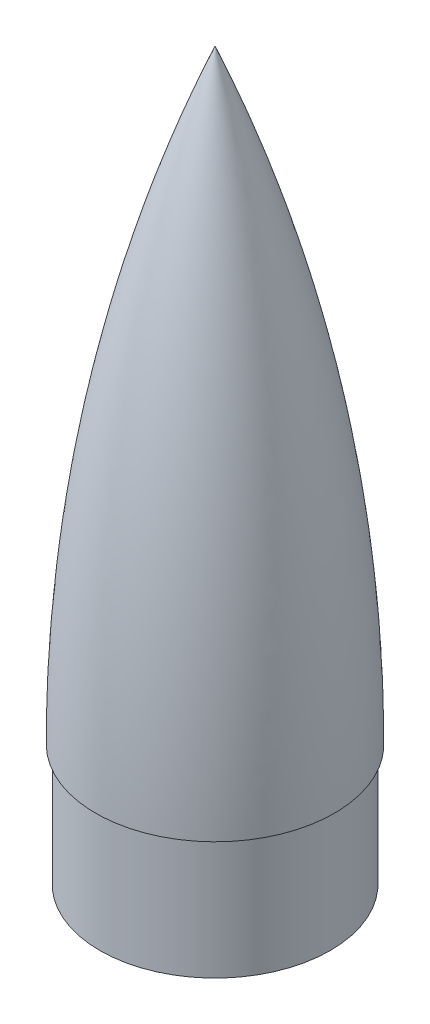
SolidWorks part; units mm, degrees
ref_plane "Front Plane" through (0, 0, 0) normal (0, 0, 1) x (1, 0, 0)
ref_plane "Top Plane" through (0, 0, 0) normal (0, 1, 0) x (1, 0, 0)
ref_plane "Right Plane" through (0, 0, 0) normal (1, 0, 0) x (0, 0, -1)
sketch "Sketch1" plane through (0, 0, 0) normal (0, 0, 1) x (1, 0, 0)
  line L0 (0, 0) -> (-29.605, 0) construction
  line L1 (0, 0) -> (0, 150) construction
  line L2 (0, 0) -> (365.2009, 0) construction
  line L3 (0, 150) -> (0, 136.2973)
  line L4 (-29.605, 0) -> (-24.605, 0)
  line L5 (-28.58, 0) -> (-28.58, -30)
  line L6 (-28.58, -30) -> (-27.08, -30)
  line L7 (-27.08, -30) -> (-19.3346, 63.8832)
  circle A0 centre (365.2009, 0) radius 394.8059 construction
  circle A1 centre (365.2009, 0) radius 389.8059 construction
  arc A2 (-29.605, 0) -> (0, 150) centre (365.2009, 0) cw
  arc A3 (-19.3346, 63.8832) -> (0, 136.2973) centre (365.2009, 0) cw
  point P13 (-19.7493, 61.3349)
  dimension "D1" = 29.605
  dimension "D2" = 150
  dimension "D4" = 1.5
  dimension "D5" = 28.58
  dimension "D6" = 30
  dimension "D3" = 5
revolve "nosecone-shape" add sketch "Sketch1" angle 360 about L1 region at (-18.3725, 69.631, 0) region at (-27.118, -12.7397, 0)
sketch "Sketch2" plane through (0, 0, 0) normal (1, 0, 0) x (0, 0, -1)
  line L0 (0, 30) -> (0, 0) construction
  circle A0 centre (0, 30) radius 4
  dimension "D1" = 8
  dimension "D2" = 30
extrude "central-bar" add sketch "Sketch2" along normal up to body and the other way up to next
fillet "bar-strain-relief" radius 5 2 edges at (-21.6911, 32.0941, 3.4081) (21.6911, 32.0941, 3.4081)
equation "\"shoulder_diameter\"= 57.16mm"
equation "\"shoulder_radius\"= \"shoulder_diameter\" / 2"
equation "\"base_diameter\"= 59.21mm"
equation "\"base_radius\"= \"base_diameter\" / 2"
equation "\"D1@Sketch1\"=\"base_radius\""
equation "\"D5@Sketch1\"=\"shoulder_radius\""
equation "\"length\"= 15cm"
equation "\"D2@Sketch1\"=\"length\""
equation "\"shoulder_length\"= 3cm"
equation "\"D6@Sketch1\"=\"shoulder_length\""
equation "\"min_thickness\"= .15cm"
equation "\"D4@Sketch1\"=\"min_thickness\""
equation "\"bar_depth\"= 3cm"
equation "\"bar_radius\"= .4cm"
equation "\"D2@Sketch2\"=\"bar_depth\""
equation "\"D1@Sketch2\"=\"bar_radius\"*2"
